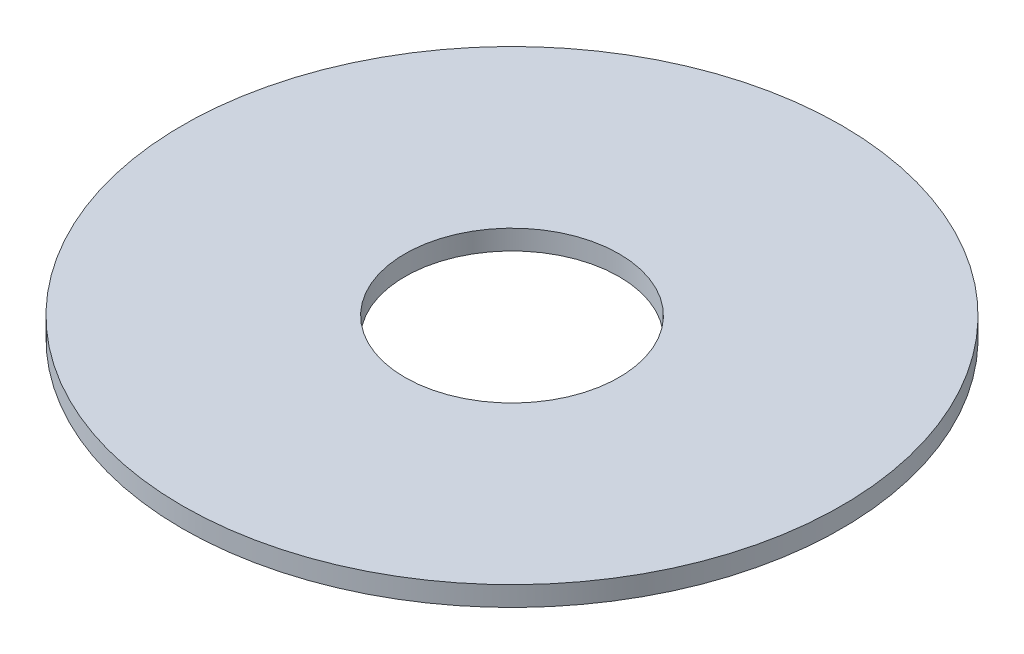
SolidWorks part; units mm, degrees
ref_plane "Front Plane" through (0, 0, 0) normal (0, 0, 1) x (1, 0, 0)
ref_plane "Top Plane" through (0, 0, 0) normal (0, 1, 0) x (1, 0, 0)
ref_plane "Right Plane" through (0, 0, 0) normal (1, 0, 0) x (0, 0, -1)
sketch "Sketch1" plane through (0, 0, 0) normal (0, 1, 0) x (1, 0, 0)
  circle A0 centre (0, 0) radius 100
  dimension "FLANGE_OD" = 200
extrude "Boss-Extrude1" add sketch "Sketch1" along normal blind 6
sketch "Sketch2" plane through (0, 0, 0) normal (0, 1, 0) x (1, 0, 0)
  circle A0 centre (0, 0) radius 32.5
  dimension "BORE_D" = 65
extrude "Cut-Extrude1" cut sketch "Sketch2" along normal through all
sketch "Sketch3" plane through (0, 6, 0) normal (0, 1, 0) x (1, 0, 0)
  circle A0 centre (0, 0) radius 18.5266 construction
  circle A1 centre (-18.5266, 0) radius 2.8607
  dimension "BOLT_D" = 5.7214
  dimension "BOLT_PCD" = 37.0533
extrude "Cut-Extrude2" cut sketch "Sketch3" against normal blind 4.6462 rebuild error yes
pattern_circular "CirPattern1" count 3 over 360 rebuild error yes
